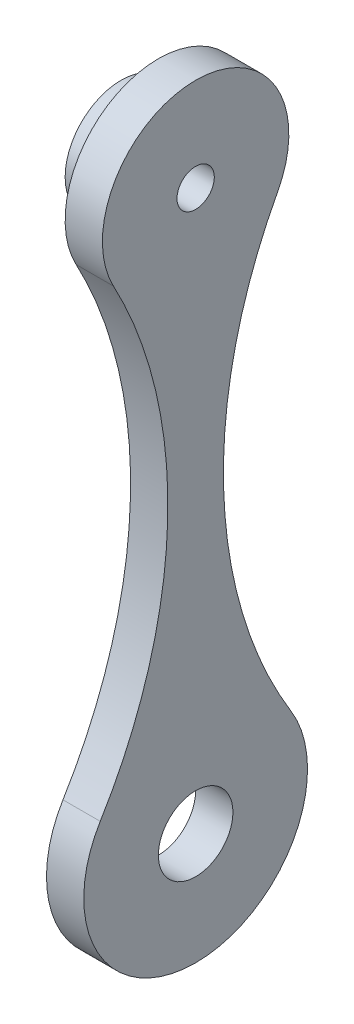
SolidWorks part; units mm, degrees
ref_plane "Front Plane" through (0, 0, 0) normal (0, 0, 1) x (1, 0, 0)
ref_plane "Top Plane" through (0, 0, 0) normal (0, 1, 0) x (1, 0, 0)
ref_plane "Right Plane" through (0, 0, 0) normal (1, 0, 0) x (0, 0, -1)
sketch "Sketch1" plane through (0, 0, 0) normal (1, 0, 0) x (0, 0, -1)
  line L0 (0, -55) -> (0, -80) construction
  line L1 (0, -80) -> (0, -230) construction
  circle A1 centre (0, -80) radius 25
  circle A3 centre (0, -80) radius 15
  circle A6 centre (0, -230) radius 30
  circle A7 centre (0, -230) radius 10
  arc A8 (-22.0405, -91.7991) -> (-25.5857, -214.3357) centre (-130.7115, -149.9746) cw
  arc A9 (22.0405, -91.7991) -> (25.5857, -214.3357) centre (130.7115, -149.9746) ccw
  point P25 (-7.5, -153.5393)
  point P26 (7.5, -153.5393)
  dimension "D2" = 50
  dimension "D5" = 10
  dimension "D7" = 60
  dimension "D8" = 15
  dimension "D9" = 150
extrude "Boss-Extrude1" add sketch "Sketch1" along normal blind 10 contours L0 A1 | L0 A1 | A1 A3 | A6 | A7 | A3 region at (0, -85.9102, -23.563) region at (0, -154.3333, 0)
sketch "Sketch3" plane through (0, 0, 0) normal (-1, 0, 0) x (0, 0, 1)
  line L0 (0, 0) -> (0, -80) construction
  circle A1 centre (0, -80) radius 15
  dimension "D2" = 30
extrude "Boss-Extrude3" add sketch "Sketch3" along normal blind 10
sketch "Sketch4" plane through (-10, 0, 0) normal (-1, 0, 0) x (0, 0, 1)
  circle A2 centre (0, -80) radius 5
  circle A3 centre (0, -80) radius 5
  dimension "D1" = 10
extrude "Cut-Extrude1" cut sketch "Sketch4" against normal blind 20
ref_axis "Axis2" through (10, -80, 0) along (-1, 0, 0)
ref_axis "Axis3" through (25.8875, -230, 0) along (-1, 0, 0)
ref_plane "Plane1" through (-5, 0, 0) normal (-1, 0, 0) x (0, 0, 1)
ref_plane "Plane2" through (5, 0, 0) normal (-1, 0, 0) x (0, 0, 1)
ref_point "Point1"
ref_point "Point2"
sketch "Sketch6" plane through (5, 0, 0) normal (-1, 0, 0) x (0, 0, 1)
  line L0 (0, -80) -> (0, -230) construction
  point P4 (0, -155)
ref_point "l4_1"
